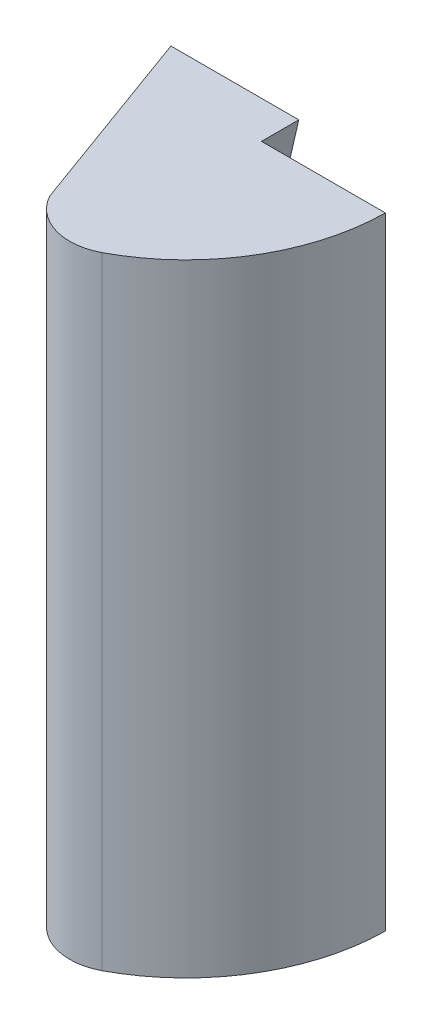
SolidWorks part; units mm, degrees
ref_plane "Front Plane" through (0, 0, 0) normal (0, 0, 1) x (1, 0, 0)
ref_plane "Top Plane" through (0, 0, 0) normal (0, 1, 0) x (1, 0, 0)
ref_plane "Right Plane" through (0, 0, 0) normal (1, 0, 0) x (0, 0, -1)
sketch "Sketch1" plane through (0, 0, 0) normal (0, 1, 0) x (1, 0, 0)
  line L0 (13.1596, 18.7939) -> (-6.8404, 18.7939)
  line L1 (-6.8404, 18.7939) -> (0, 0)
  arc A1 (0, 0) -> (13.1596, 18.7939) centre (-2.8171, 15.9767) ccw
  dimension "D1" = 70
  dimension "D2" = 20
  dimension "D3" = 20
extrude "Boss-Extrude1" add sketch "Sketch1" along normal blind 50
sketch "Sketch3" plane through (0, 0, -18.7939) normal (0, 0, -1) x (-1, 0, 0)
  line L0 (-13.1596, 0) -> (6.8404, 0) construction
  line L1 (-13.1596, 50) -> (6.8404, 50) construction
  line L2 (6.8404, 50) -> (6.8404, 0) construction
  circle A0 centre (-3.1596, 19) radius 1.6
  circle A1 centre (-3.1596, 31) radius 1.6
  dimension "D1" = 3.2
  dimension "D2" = 3.2
  dimension "D3" = 12
  dimension "D4" = 19
  dimension "D5" = 19
  dimension "D6" = 10
sketch "Sketch5" plane through (0, 50, 0) normal (0, 1, 0) x (1, 0, 0)
  line L0 (-6.8404, 18.7939) -> (0, 0) construction
  line L1 (-1.2659, 3.4781) -> (-6.8404, 18.7939)
  line L2 (-6.8404, 18.7939) -> (13.1596, 18.7939)
  arc A0 (-1.2659, 3.4781) -> (4.8351, 1.6716) centre (2.6878, 5.6254) ccw
  arc A1 (0, 0) -> (13.1596, 18.7939) centre (-2.8171, 15.9767) ccw construction
  arc A2 (13.1596, 18.7939) -> (0, 0) centre (-2.8171, 15.9767) cw
  arc M1 (0, 0) -> (13.1596, 18.7939) centre (-2.8171, 15.9767) ccw
  line M3 (-6.8404, 18.7939) -> (0, 0)
extrude "Cut-Extrude1" cut sketch "Sketch5" against normal blind 50 contours A0 M3 M1 region at (0.8039, 50, -1.1091)
extrude "Cut-Extrude2" cut sketch "Sketch3" against normal blind 15 contours A0 | A1
sketch "Sketch6" plane through (0, 0, -18.7939) normal (0, 0, -1) x (-1, 0, 0)
  line L0 (-3.1596, 31) -> (-7.5461, 50) construction
  line L1 (-13.1596, 50) -> (6.8404, 50) construction
  line L2 (-13.1596, 50) -> (-13.1596, 0) construction
  line L3 (-5.3528, 40.5) -> (-1.4554, 41.3998) construction
  line L4 (-3.1596, 31) -> (0.7379, 31.8998) construction
  line L5 (0.7379, 31.8998) -> (-1.4554, 41.3998)
  line L6 (-1.4554, 41.3998) -> (-3.4409, 50)
  line L7 (-3.4409, 50) -> (-7.5461, 50)
  line L8 (-7.5461, 50) -> (-13.1596, 50)
  line L9 (0.9456, 31) -> (-3.1596, 31) construction
  line L10 (0.9456, 31) -> (0.7379, 31.8998) construction
  line L11 (0.7379, 31.8998) -> (0.9456, 31)
  line L12 (-3.1596, 31) -> (-3.1596, 19) construction
  line L13 (-3.1596, 25) -> (6.8404, 25) construction
  line L14 (6.8404, 50) -> (6.8404, 0) construction
  line L15 (6.8404, 25) -> (-13.1596, 25) construction
  line L16 (0.9456, 31) -> (0.9456, 19)
  line L17 (0.9456, 31) -> (0.9456, 36)
  line L18 (0.9456, 36) -> (-0.2087, 36)
  line L19 (0.7379, 18.1002) -> (0.9456, 19)
  line L20 (0.9456, 19) -> (0.9456, 14)
  line L21 (0.9456, 14) -> (-0.2087, 14)
  line L22 (0.7379, 18.1002) -> (-1.4554, 8.6002)
  line L23 (-1.4554, 8.6002) -> (-3.4409, 0)
  line L24 (-3.4409, 0) -> (-7.5461, 0)
  line L25 (-7.5461, 0) -> (-13.1596, 0)
  line L26 (-13.1596, 0) -> (-13.1596, 50)
  line L28 (0.9456, 36) -> (1.9456, 36)
  line L29 (0.9456, 36) -> (0.9456, 14)
  line L30 (0.9456, 14) -> (1.9456, 14)
  line L31 (1.9456, 36) -> (1.9456, 14)
  point P26 (0.9456, 25)
  circle M14 centre (-3.1596, 19) radius 1.6
  circle M15 centre (-3.1596, 31) radius 1.6
  line M16 (-13.1596, 0) -> (6.8404, 0)
  line M18 (6.8404, 50) -> (-13.1596, 50)
  line M19 (-13.1596, 50) -> (-13.1596, 0)
  dimension "D1" = 13
  dimension "D2" = 4
  dimension "D3" = 4
  dimension "D4" = 90
  dimension "D5" = 5
  dimension "D6" = 1
extrude "Cut-Extrude4" cut sketch "Sketch6" against normal blind 3 contours L23 L22 L19 L16 L11 L5 L6 M18 M19 M16 M15 M14 | L17 L18 L5 L11 | L19 L22 L21 L20 region at (6.9543, 25, -18.7939) region at (-0.5608, 34.3333, -18.7939) region at (-0.5608, 15.6667, -18.7939)
sketch "Sketch7" plane through (0, 0, -18.7939) normal (0, 0, -1) x (-1, 0, 0)
  line L1 (-13.1596, 0) -> (-14.8261, 0)
  line L2 (-13.1596, 0) -> (-13.1596, 50)
  line L3 (-13.1596, 50) -> (-14.8261, 50)
  line L4 (-14.8261, 0) -> (-14.8261, 50)
extrude "Cut-Extrude5" cut sketch "Sketch7" against normal blind 3
extrude "Cut-Extrude6" cut sketch "Sketch6<5>" against normal blind 3 contours L31 L28 L17 L16 L20 L30 region at (-1.4456, 25, -18.7939)
sketch "Sketch6<5>" plane through (0, 0, -18.7939) normal (0, 0, -1) x (-1, 0, 0) same geometry as "Sketch6"
